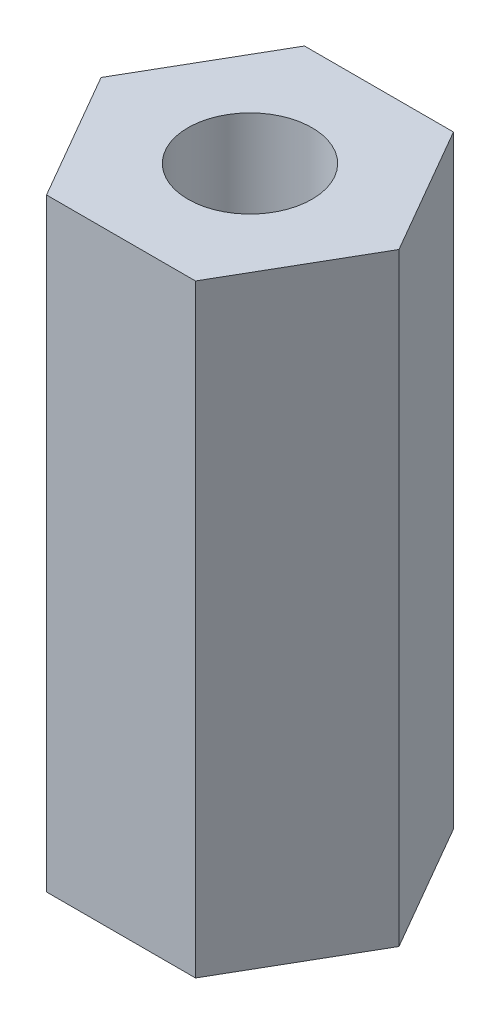
SolidWorks part; units mm, degrees
material "Brass"
ref_plane "Front" through (0, 0, 0) normal (0, 0, 1) x (1, 0, 0)
ref_plane "Top" through (0, 0, 0) normal (0, 1, 0) x (1, 0, 0)
ref_plane "Right" through (0, 0, 0) normal (1, 0, 0) x (0, 0, -1)
sketch "Sketch1" plane through (0, 0, 0) normal (0, 1, 0) x (1, 0, 0)
  line L1 (2.702, 0) -> (1.351, 2.34)
  line L2 (1.351, 2.34) -> (-1.351, 2.34)
  line L3 (-1.351, 2.34) -> (-2.702, 0)
  line L4 (-2.702, 0) -> (-1.351, -2.34)
  line L5 (-1.351, -2.34) -> (1.351, -2.34)
  line L6 (1.351, -2.34) -> (2.702, 0)
  circle A0 centre (0, 0) radius 2.34 construction
  dimension "D1" = 4.68
extrude "Boss-Extrude1" add sketch "Sketch1" along normal blind 10.95
hole_wizard "Ø2.25 (2.25) Diameter Hole1" positions "Sketch4" profile "Sketch3" hole size "Ø2.25" standard "ANSI Metric" end condition through all
sketch "Sketch4" plane through (0, 10.95, 0) normal (0, 1, 0) x (1, 0, 0)
  point P0 (0, 0)
sketch "Sketch3" plane through (0, 10.95, 0) normal (1, 0, 0) x (0, 0, 1)
  line L0 (0, 0) -> (0, 10.95)
  line L1 (0, 10.95) -> (1.125, 10.95)
  line L2 (1.125, 10.95) -> (1.125, 0)
  line L5 (1.125, 0) -> (0, 0)
  line L11 (0, -6.35) -> (0, 107.95) construction
  dimension "Thru Hole Dia." = 2.25
  dimension "Thru Hole Depth" = 10.95
